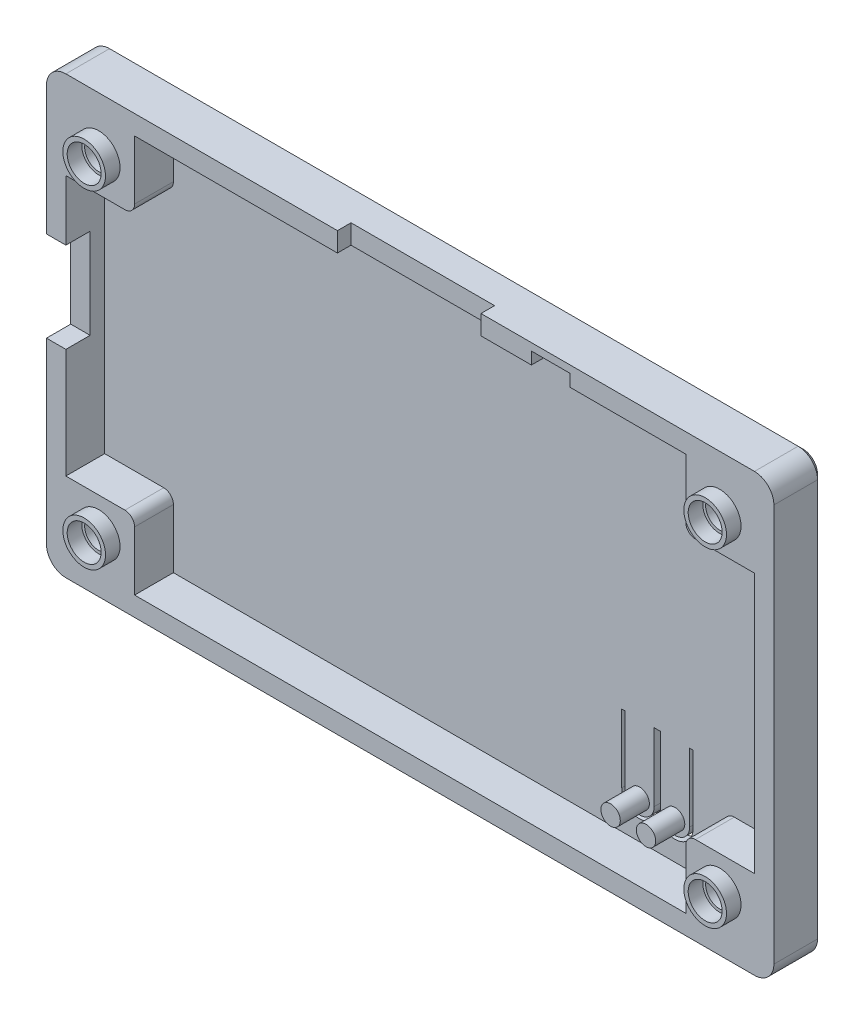
SolidWorks part; units mm, degrees
ref_plane "Přední rovina" through (0, 0, 0) normal (0, 0, 1) x (1, 0, 0)
ref_plane "Horní rovina" through (0, 0, 0) normal (0, 1, 0) x (1, 0, 0)
ref_plane "Pravá rovina" through (0, 0, 0) normal (1, 0, 0) x (0, 0, -1)
sketch "Skica1" plane through (0, 0, 0) normal (0, 0, 1) x (1, 0, 0)
  line L1 (-37.5, -22.5) -> (37.5, -22.5)
  line L2 (-37.5, -22.5) -> (-37.5, 22.5)
  line L3 (-37.5, 22.5) -> (37.5, 22.5)
  line L4 (37.5, -22.5) -> (37.5, 22.5)
  line L5 (-37.5, -22.5) -> (37.5, 22.5) construction
  line L6 (-37.5, 22.5) -> (37.5, -22.5) construction
  point P0 (0, 0)
  dimension "D1" = 75
  dimension "D2" = 45
extrude "Přidat vysunutím1" add sketch "Skica1" along normal blind 13
sketch "Skica2" plane through (0, 0, 13) normal (0, 0, 1) x (1, 0, 0)
  line L0 (37.5, 22.5) -> (-37.5, 22.5) construction
  line L1 (-35.5, -20.5) -> (35.5, -20.5)
  line L2 (-35.5, -20.5) -> (-35.5, 20.5)
  line L3 (-35.5, 20.5) -> (35.5, 20.5)
  line L4 (35.5, -20.5) -> (35.5, 20.5)
  line L5 (-35.5, -20.5) -> (35.5, 20.5) construction
  line L6 (-35.5, 20.5) -> (35.5, -20.5) construction
  line L7 (37.5, -22.5) -> (37.5, 22.5) construction
  point P0 (0, 0)
  dimension "D1" = 2
  dimension "D2" = 2
extrude "Odebrat vysunutím1" cut sketch "Skica2" against normal blind 12
fillet "Zaoblit1" radius 2 8 edges at (37.5, 22.5, 6.5) (37.5, -22.5, 6.5) (-37.5, -22.5, 6.5) (-37.5, 22.5, 6.5) (35.5, -20.5, 7) (35.5, 20.5, 7) (-35.5, -20.5, 7) (-35.5, 20.5, 7)
chamfer "Zkosení2" distance 0.5 angle 45 8 edges at (-36.9142, 21.9142, 0) (-37.5, 0, 0) (-36.9142, -21.9142, 0) (0, -22.5, 0) (36.9142, -21.9142, 0) (37.5, 0, 0) (36.9142, 21.9142, 0) (0, 22.5, 0)
sketch "Skica4" plane through (0, 0, 1) normal (0, 0, 1) x (1, 0, 0)
  line L1 (-28.4142, 13.4142) -> (-36.9142, 13.4142)
  line L2 (-28.4142, 13.4142) -> (-28.4142, 21.9142)
  line L3 (-28.4142, 21.9142) -> (-36.9142, 21.9142)
  line L4 (-36.9142, 13.4142) -> (-36.9142, 21.9142)
  line L5 (-36.9142, -21.9142) -> (-28.4142, -21.9142)
  line L6 (-36.9142, -21.9142) -> (-36.9142, -13.4142)
  line L7 (-36.9142, -13.4142) -> (-28.4142, -13.4142)
  line L8 (-28.4142, -21.9142) -> (-28.4142, -13.4142)
  line L9 (36.9142, -21.9142) -> (28.4142, -21.9142)
  line L10 (36.9142, -21.9142) -> (36.9142, -13.4142)
  line L11 (36.9142, -13.4142) -> (28.4142, -13.4142)
  line L12 (28.4142, -21.9142) -> (28.4142, -13.4142)
  line L13 (36.9142, 21.9142) -> (28.4142, 21.9142)
  line L14 (36.9142, 21.9142) -> (36.9142, 13.4142)
  line L15 (36.9142, 13.4142) -> (28.4142, 13.4142)
  line L16 (28.4142, 21.9142) -> (28.4142, 13.4142)
  arc A1 (-37.5, -20.5) -> (-35.5, -22.5) centre (-35.5, -20.5) ccw construction
  arc A2 (-35.5, 22.5) -> (-37.5, 20.5) centre (-35.5, 20.5) ccw construction
  arc A3 (35.5, -22.5) -> (37.5, -20.5) centre (35.5, -20.5) ccw construction
  arc A4 (37.5, 20.5) -> (35.5, 22.5) centre (35.5, 20.5) ccw construction
  dimension "D1" = 8.5
  dimension "D2" = 8.5
  dimension "D3" = 8.5
  dimension "D4" = 8.5
  dimension "D5" = 8.5
  dimension "D6" = 8.5
  dimension "D7" = 8.5
  dimension "D8" = 8.5
extrude "Přidat vysunutím2" add sketch "Skica4" along normal blind 4.22
fillet "Zaoblit2" radius 1 4 edges at (28.4142, -13.4142, 3.11) (28.4142, 13.4142, 3.11) (-28.4142, -13.4142, 3.11) (-28.4142, 13.4142, 3.11)
sketch "Skica5" plane through (0, 0, 13) normal (0, 0, 1) x (1, 0, 0)
  line L1 (-32.5752, 7.2) -> (-42.6609, 7.2)
  line L2 (-32.5752, 7.2) -> (-32.5752, -2.1)
  line L3 (-32.5752, -2.1) -> (-42.6609, -2.1)
  line L4 (-42.6609, 7.2) -> (-42.6609, -2.1)
  line L5 (-35.5, -22.5) -> (35.5, -22.5) construction
  dimension "D1" = 20.4
  dimension "D2" = 9.3
sketch "Skica6" plane through (0, -22.5, 0) normal (0, -1, 0) x (1, 0, 0)
  line L0 (35.5, 0) -> (-35.5, 0) construction
  line L1 (-48.5537, 21.9141) -> (43.6554, 21.9141)
  line L2 (-48.5537, 21.9141) -> (-48.5537, 5)
  line L3 (-48.5537, 5) -> (43.6554, 5)
  line L4 (43.6554, 21.9141) -> (43.6554, 5)
  dimension "D1" = 5
extrude "Odebrat vysunutím3" cut sketch "Skica6" against normal blind 64.22
extrude "Odebrat vysunutím4" cut sketch "Skica5" against normal blind 10.5
sketch "Skica7" plane through (0, 0, 5) normal (0, 0, 1) x (1, 0, 0)
  line L1 (12.5, 21.75) -> (16.5, 21.75)
  line L2 (12.5, 21.75) -> (12.5, 14.2045)
  line L3 (12.5, 14.2045) -> (16.5, 14.2045)
  line L4 (16.5, 21.75) -> (16.5, 14.2045)
  line L5 (37.5, 20.5) -> (37.5, -20.5) construction
  line L6 (-35.5, 22.5) -> (35.5, 22.5) construction
  dimension "D1" = 21
  dimension "D2" = 4
  dimension "D3" = 0.75
extrude "Odebrat vysunutím5" cut sketch "Skica7" against normal blind 1.9
sketch "Skica8" plane through (0, 0, 5) normal (0, 0, 1) x (1, 0, 0)
  line L1 (-7.5, 24.2167) -> (7.3, 24.2167)
  line L2 (-7.5, 24.2167) -> (-7.5, 16.9244)
  line L3 (-7.5, 16.9244) -> (7.3, 16.9244)
  line L4 (7.3, 24.2167) -> (7.3, 16.9244)
  line L5 (-37.5, 7.2) -> (-37.5, 20.5) construction
  dimension "D1" = 30
  dimension "D2" = 14.8
extrude "Odebrat vysunutím6" cut sketch "Skica8" against normal blind 1.4
sketch "Skica9" plane through (0, 0, 1) normal (0, 0, 1) x (1, 0, 0)
  line L0 (-37.5, -20.5) -> (-37.5, -2.1) construction
  line L8 (-35.5, -22.5) -> (35.5, -22.5) construction
  line L9 (-37.5, 7.2) -> (-37.5, 20.5) construction
  line L11 (-35.5, 22.5) -> (-7.5, 22.5) construction
  line L13 (37.5, 20.5) -> (37.5, -20.5) construction
  line L15 (7.3, 22.5) -> (35.5, 22.5) construction
  circle A0 centre (-32.1142, 16.9142) radius 1.45
  circle A1 centre (-32.1142, -16.9142) radius 1.45
  circle A2 centre (31.9142, -16.9142) radius 1.45
  circle A3 centre (31.9142, 16.9142) radius 1.45
  dimension "D1" = 2.9
  dimension "D4" = 2.9
  dimension "D5" = 2.9
  dimension "D6" = 2.9
  dimension "D2" = 5.3858
  dimension "D3" = 5.5858
  dimension "D7" = 5.3858
  dimension "D8" = 5.5858
  dimension "D9" = 5.5858
  dimension "D10" = 5.5858
  dimension "D11" = 5.5858
  dimension "D12" = 5.5858
extrude "Odebrat vysunutím7" cut sketch "Skica9" against normal mid plane 10
sketch "Skica10" plane through (0, 0, 5) normal (0, 0, 1) x (1, 0, 0)
  circle A0 centre (31.9142, 16.9142) radius 1.75
  circle A1 centre (31.9142, 16.9142) radius 2.2
  circle A2 centre (31.9142, -16.9142) radius 1.75
  circle A3 centre (31.9142, -16.9142) radius 2.2
  circle A4 centre (-32.1142, -16.9142) radius 1.75
  circle A5 centre (-32.1142, -16.9142) radius 2.2
  circle A6 centre (-32.1142, 16.9142) radius 1.75
  circle A7 centre (-32.1142, 16.9142) radius 2.2
  dimension "D1" = 3.5
  dimension "D2" = 4.4
  dimension "D3" = 3.5
  dimension "D4" = 3.5
  dimension "D5" = 3.5
  dimension "D6" = 4.4
  dimension "D7" = 4.4
  dimension "D8" = 4.4
extrude "Přidat vysunutím3" add sketch "Skica10" along normal blind 1.5
sketch "Skica11" plane through (0, 0, 0) normal (0, 0, -1) x (-1, 0, 0)
  circle A0 centre (32.1142, -16.9142) radius 1.45
  circle A1 centre (32.1142, -16.9142) radius 2.925
  circle A2 centre (32.1142, 16.9142) radius 1.45
  circle A3 centre (-31.9142, 16.9142) radius 1.45
  circle A4 centre (-31.9142, -16.9142) radius 1.45
  circle A5 centre (-31.9142, -16.9142) radius 2.925
  circle A6 centre (-31.9142, 16.9142) radius 2.925
  circle A7 centre (32.1142, 16.9142) radius 2.925
  dimension "D1" = 5.85
  dimension "D2" = 5.85
  dimension "D3" = 5.85
  dimension "D4" = 5.85
extrude "Odebrat vysunutím8" cut sketch "Skica11" against normal blind 2
sketch "Skica12" plane through (0, 0, 1) normal (0, 0, 1) x (1, 0, 0)
  line L0 (-28.4142, -20.5) -> (28.4142, -20.5) construction
  circle A0 centre (23.3142, -16.6) radius 1
  circle A1 centre (19.6642, -16.6) radius 1
  point P2 (31.9142, -16.9142)
  dimension "D2" = 2
  dimension "D4" = 2
  dimension "D1" = 8.6
  dimension "D3" = 3.9
  dimension "D5" = 3.65
extrude "Přidat vysunutím4" add sketch "Skica12" along normal blind 3
sketch "Skica13" plane through (0, 0, 1) normal (0, 0, 1) x (1, 0, 0)
  line L0 (23.3142, -16.6) -> (23.3142, -9.5563) construction
  line L1 (21.8142, -16.6) -> (21.8142, -9.5563)
  line L2 (24.8142, -16.6) -> (24.8142, -9.5563)
  line L3 (23.3142, -9.5563) -> (23.3142, -16.6) construction
  line L4 (25.1642, -9.5563) -> (25.1642, -16.6)
  line L6 (25.1642, -9.5563) -> (21.4642, -9.5563)
  line L7 (19.6642, -16.6) -> (19.6642, -9.5563) construction
  line L8 (18.1642, -16.6) -> (18.1642, -9.5563)
  line L9 (21.1642, -16.6) -> (21.1642, -9.5563)
  line L10 (19.6642, -16.6) -> (19.6642, -9.5563) construction
  line L11 (17.8142, -16.6) -> (17.8142, -9.5563)
  line L13 (21.4642, -9.5563) -> (17.8142, -9.5563)
  arc A0 (21.8142, -16.6) -> (24.8142, -16.6) centre (23.3142, -16.6) ccw
  arc A2 (21.4892, -9.2531) -> (21.4642, -9.5563) centre (23.3142, -9.5563) ccw
  arc A3 (21.4892, -16.9031) -> (25.1642, -16.6) centre (23.3142, -16.6) ccw
  circle A4 centre (23.3142, -16.6) radius 1 construction
  circle A5 centre (23.3142, -16.6) radius 1 construction
  arc A6 (18.1642, -16.6) -> (21.1642, -16.6) centre (19.6642, -16.6) ccw
  circle A8 centre (19.6642, -16.6) radius 1 construction
  arc A9 (17.8142, -16.6) -> (21.4892, -16.9031) centre (19.6642, -16.6) ccw
  arc A10 (21.5142, -9.5563) -> (21.4892, -9.2531) centre (19.6642, -9.5563) ccw
  circle A11 centre (19.6642, -16.6) radius 1 construction
  point P3 (23.3142, -13.0781)
  point P8 (23.3142, -13.0781)
  point P24 (19.6642, -13.0781)
  point P33 (19.6642, -13.0781)
  dimension "D1" = 0.5
  dimension "D2" = 0.85
  dimension "D3" = 0.5
  dimension "D4" = 0.85
extrude "Odebrat vysunutím14" cut sketch "Skica13" against normal blind 1 contours L11 A9 A3 L4 L6 L2 A0 L1 L13 L9 A6 L8 region at (21.4892, -14.3585, 1)
chamfer "Zkosení3" distance 2 angle 45 2 edges at (30.4642, 16.9142, 2) (-33.5642, -16.9142, 2)
chamfer "Zkosení4" distance 2 angle 45 2 edges at (30.4642, -16.9142, 2) (-33.5642, 16.9142, 2)
